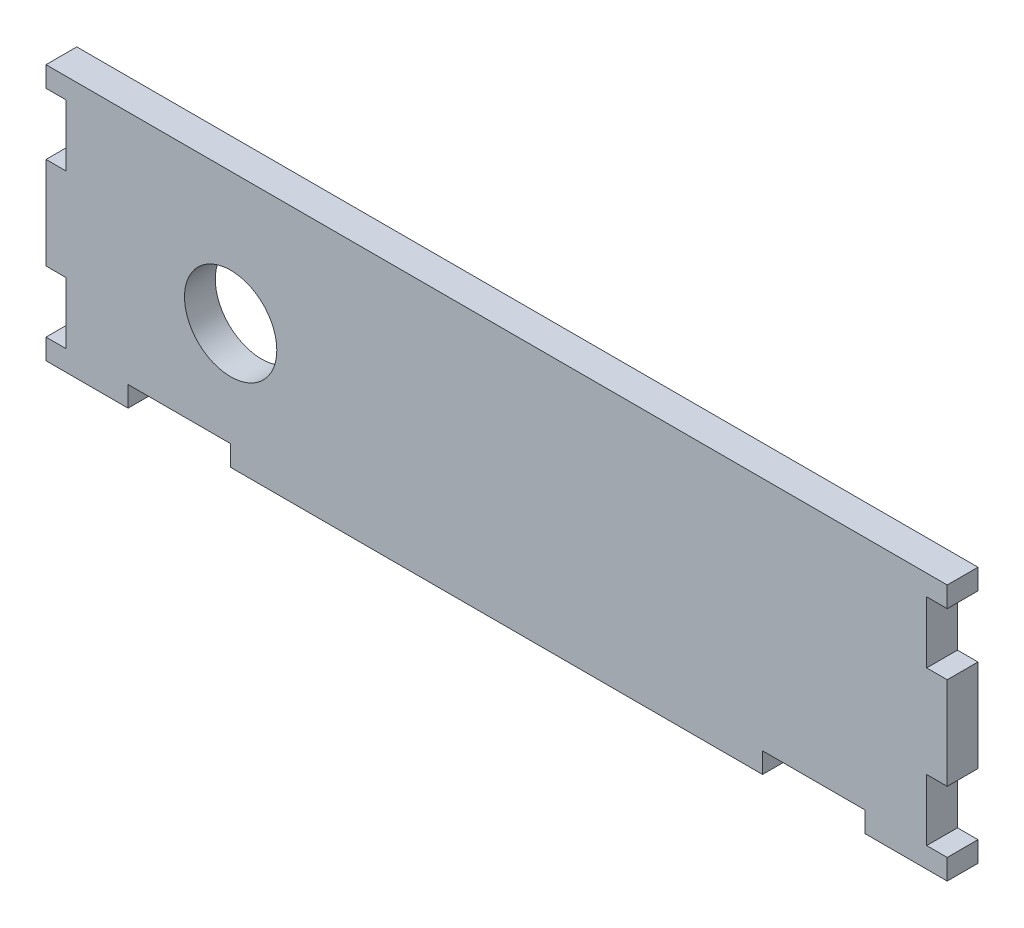
SolidWorks part; units mm, degrees
ref_plane "Plano frontal" through (0, 0, 0) normal (0, 0, 1) x (1, 0, 0)
ref_plane "Plano superior" through (0, 0, 0) normal (0, 1, 0) x (1, 0, 0)
ref_plane "Plano direito" through (0, 0, 0) normal (1, 0, 0) x (0, 0, -1)
sketch "Esboço1" plane through (0, 0, 0) normal (0, 0, 1) x (1, 0, 0)
  line L0 (54.3814, -10.6678) -> (-10.9255, -10.6678)
  line L1 (-8.9871, 12.3322) -> (-8.9871, -8.6678)
  line L2 (-10.9255, 12.3322) -> (-8.9871, 12.3322)
  line L3 (-10.9255, -8.6678) -> (76.9288, -8.6678)
  line L4 (76.9288, 14.3322) -> (76.9288, -8.6678)
  line L5 (-10.9255, -10.6678) -> (-8.9255, -10.6678)
  line L6 (76.9288, 14.3322) -> (-10.9255, 14.3322)
  line L7 (76.9288, -8.6678) -> (76.9288, -10.6678)
  line L8 (-8.9255, 14.3322) -> (-10.9255, 14.3322)
  line L9 (-8.9871, 12.3322) -> (-8.9871, -2.6678)
  line L10 (66.0745, 14.3322) -> (54.0745, 14.3322)
  line L11 (-8.9871, 6.3322) -> (-10.9255, 6.3322)
  line L12 (-10.9255, 14.3322) -> (-10.9255, -8.6678)
  line L13 (-10.9255, 6.3322) -> (-10.9255, -8.6678)
  line L14 (-10.9255, 14.3322) -> (-8.9255, 14.3322)
  line L15 (-8.9871, -2.6678) -> (-8.9871, -6.6678)
  line L16 (-10.9255, -2.6678) -> (-8.9871, -2.6678)
  line L17 (76.9288, -10.6678) -> (54.3814, -10.6678)
  line L18 (-2.9255, -10.6678) -> (-2.9255, -8.6678)
  line L19 (7.0745, -8.6678) -> (7.0745, -10.6678)
  line L20 (58.9288, -8.6678) -> (58.9288, -10.6678)
  line L21 (68.9288, -8.6678) -> (68.9288, -10.6678)
  line L22 (74.9288, 14.3322) -> (74.9288, -8.6678)
  line L23 (74.9288, 12.3322) -> (76.9288, 12.3322)
  line L24 (28.5745, 14.3322) -> (16.5745, 14.3322)
  line L25 (-10.9255, -8.6678) -> (-8.9871, -8.6678)
  line L26 (74.9288, 6.3322) -> (76.9288, 6.3322)
  line L27 (54.3814, -10.6678) -> (42.3814, -10.6678)
  line L28 (74.9288, -2.6678) -> (76.9288, -2.6678)
  line L29 (15.7279, -10.6678) -> (27.7279, -10.6678)
  line L32 (-8.9871, 12.3322) -> (-8.9871, 6.3322)
  line L34 (-10.9255, -8.6678) -> (-10.9255, -10.6678)
  circle A0 centre (24.3545, 1.4822) radius 2
  circle A1 centre (41.8545, 1.4822) radius 2
  circle A2 centre (24.3545, 1.4822) radius 14.5
  circle A3 centre (24.3545, 1.4822) radius 4
  circle A4 centre (41.8545, 1.4822) radius 4
  circle A5 centre (41.8545, 1.4822) radius 14.5
  circle A7 centre (7.0745, 1.4822) radius 4.5
  point P4 (24.0129, -8.6678)
  point P5 (24.0129, -8.6678)
  dimension "D4" = 4
  dimension "D6" = 8
  dimension "D9" = 10.15
  dimension "D17" = 9
  dimension "D11" = 29
  dimension "D13" = 29
  dimension "D23" = 4
  dimension "D24" = 8
  dimension "D3" = 8
  dimension "D5" = 10.15
  dimension "D7" = 17.5
  dimension "D8" = 17.5
  dimension "D10" = 17.28
  dimension "D12" = 2
  dimension "D14" = 2
  dimension "D15" = 6
  dimension "D16" = 8
  dimension "D18" = 10
  dimension "D19" = 8
  dimension "D20" = 10
  dimension "D21" = 12
  dimension "D22" = 2
extrude "Ressalto-extrusão1" add sketch "Esboço1" against normal blind 3 contours A7 A2 L6 L12 L2 L1 L9 L3 | L12 L16 L9 L11 | L3 L34 L0 L18 | A7 A2 L3 A5 A3 L24 | A2 A5 A3 L3 A4 | L6 A5 A2 A4 L3 | A5 L3 L22 L6 | A5 L6 A2 | L22 L23 L4 L6 | L22 L28 L4 L26 | L3 L21 L17 L7 | A5 L0 L17 L20 L3 | L27 A5 L3 A2 L0 | A5 L3 A2 L0 | A2 L3 L19 L0 | A2 A4 A1 | A5 A3 A0 | A3 A5 | A2 A4 | A5 A2 L0 | L3 A5 A2 | A1 | A0 region at (11.1325, -9.718, 0) region at (23.7514, -9.6566, 0) region at (-6.9255, -9.6678, 0) region at (0.6374, 3.4021, 0) region at (20.0434, 2.9667, 0) region at (33.1045, -10.4744, 0) region at (33.1045, 1.6252, 0) region at (33.1045, -9.1503, 0) region at (42.4576, -9.6566, 0) region at (46.3681, 2.9348, 0) region at (27.7981, 1.4822, 0) region at (20.4621, 1.4822, 0) region at (54.9728, -9.7194, 0) region at (64.6481, 3.0982, 0) region at (38.4109, 1.4822, 0) region at (38.9116, 0.2691, 0) region at (-9.9563, 1.8322, 0) region at (33.1045, 13.9159, 0) region at (72.9288, -9.6678, 0) region at (75.9288, 1.8322, 0) region at (75.9288, 13.3322, 0)
extrude "Ressalto-extrusão2" add sketch "Esboço1<9>" against normal blind 5.5 contours A2 A4 A1 | A5 A3 A0 | A3 A5 | A2 A4 region at (27.7981, 1.4822, 0) region at (20.4621, 1.4822, 0) region at (38.4109, 1.4822, 0) region at (38.9116, 0.2691, 0)
sketch "Esboço1<9>" plane through (0, 0, 0) normal (0, 0, 1) x (1, 0, 0) same geometry as "Esboço1"
